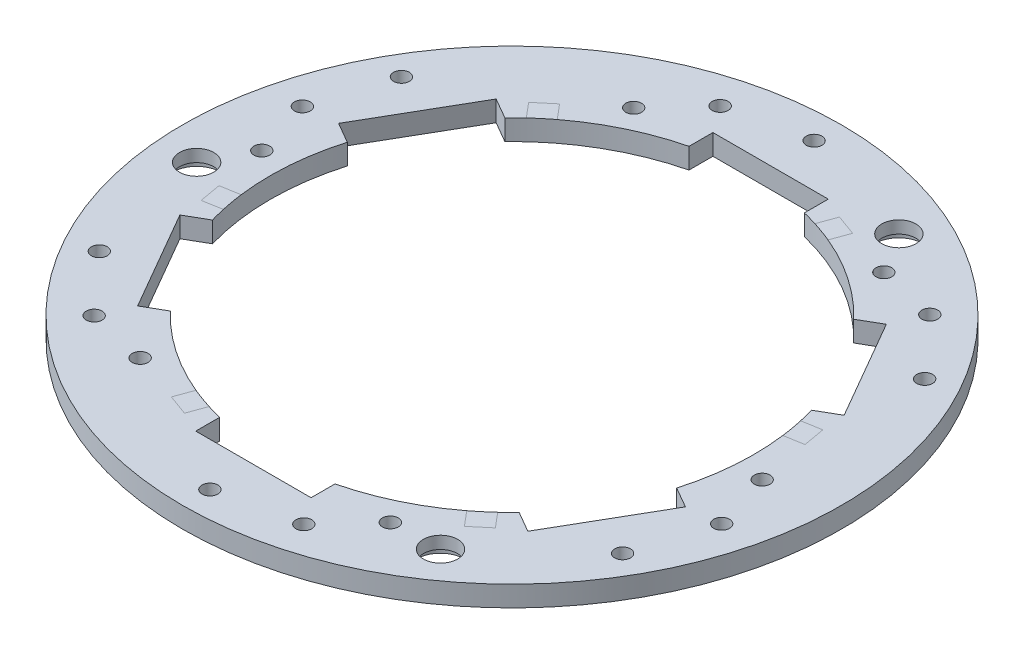
SolidWorks part; units mm, degrees
material "6061 Alloy"
ref_plane "Front Plane" through (0, 0, 0) normal (0, 0, 1) x (1, 0, 0)
ref_plane "Top Plane" through (0, 0, 0) normal (0, 1, 0) x (1, 0, 0)
ref_plane "Right Plane" through (0, 0, 0) normal (1, 0, 0) x (0, 0, -1)
sketch "Sketch1" plane through (0, 0, 0) normal (0, 1, 0) x (1, 0, 0)
  line L0 (-13.335, -54.2656) -> (-13.335, -58.1814)
  line L1 (13.335, -54.2656) -> (13.335, -58.1814)
  line L2 (-13.335, -59.7901) -> (13.335, -59.7901)
  line L3 (13.335, -58.1814) -> (13.335, -59.7901)
  line L4 (-13.335, -58.1814) -> (-13.335, -59.7901)
  line L5 (0, 0) -> (-67.0539, -5.8665) construction
  line L6 (0, 0) -> (0, -23.1086) construction
  line L7 (0, 0) -> (17.8146, -65.9496) construction
  line L8 (0, 0) -> (27.4515, -55.5868) construction
  circle A0 centre (0, 0) radius 55.88
  circle A1 centre (0, 0) radius 76.2
  circle A2 centre (0, 0) radius 59.69
  circle A3 centre (0, -69.85) radius 1.8288
  circle A4 centre (-67.0539, -5.8665) radius 3.9561
  circle A5 centre (17.8146, -65.9496) radius 1.8288
  circle A6 centre (27.4515, -55.5868) radius 1.8288
  dimension "D1" = 111.76
  dimension "D2" = 152.4
  dimension "D8" = 3.6576
  dimension "D11" = 7.9121
  dimension "D12" = 3.6576
  dimension "D15" = 3.6576
  dimension "D4" = 13.335
  dimension "D5" = 13.335
  dimension "D7" = 69.85
  dimension "D6" = 5.5245
  dimension "D9" = 67.31
  dimension "D10" = 85
  dimension "D13" = 17.8146
  dimension "D14" = 68.3133
  dimension "D16" = 61.9958
  dimension "D17" = 14.1512
  dimension "D3" = 3.81
extrude "Boss-Extrude1" add sketch "Sketch1" along normal blind 4.7625 contours L1 A2 L0 A0 | A1 A2 A0 region at (-15.0127, 0, 56.2235) region at (-74.0447, 0, 0)
pattern_circular "CirPattern1" count 6 over 360 about axis through (0, 4.7625, 0) along (0, 1, 0) of face at (-13.335, 2.3813, 57.0278) of face at (13.335, 2.3813, 57.0278) of face at (0, 4.7625, 71.6788) of face at (0, 2.3813, 59.7901)
sketch "Sketch2" plane through (0, 0, 0) normal (1, 0, 0) x (0, 0, -1)
  line L0 (76.2, 4.7625) -> (-76.2, 4.7625) construction
  line L1 (-76.2, 0) -> (76.2, 0) construction
  line L2 (76.2, 4.7625) -> (-76.2, 4.7625)
  line L3 (-76.2, 0) -> (76.2, 0)
  line L4 (0, 0) -> (0, 4.7625) construction
  circle A0 centre (-75.2856, 0) radius 2.667
  dimension "D1" = 5.334
  dimension "D2" = 0.9144
revolve "Cut-Revolve1" [suppressed] cut sketch "Sketch2" angle 360 about L4
sketch "Sketch4" plane through (0, 0, 0) normal (0, -1, 0) x (1, 0, 0)
  line L0 (0, 0) -> (-67.0539, 5.8665) construction
  line L1 (0, 0) -> (0, -39.7137) construction
  circle A0 centre (-67.0539, 5.8665) radius 5.588
  circle A2 centre (-67.0539, 5.8665) radius 3.9561 construction
  circle A3 centre (-67.0539, 5.8665) radius 3.9561
  dimension "D2" = 11.176
extrude "Cut-Extrude1" cut sketch "Sketch4" against normal blind 1.905 contours A0 region at (-72.4838, 0, 5.8665)
pattern_circular "CirPattern2" count 3 over 360 about axis through (0, 0, 0) along (0, 1, 0) of face at (-67.0539, 4.7625, 9.8225) of face at (-67.0539, 1.905, 1.9104) of face at (-67.0539, 1.905, 0.2785)
sketch "Sketch5" plane through (0, 4.7625, 0) normal (0, 1, 0) x (1, 0, 0)
  line L0 (0, 0) -> (-20.0894, -55.1952)
  line L1 (0, 0) -> (0, -18.6852)
  line L2 (-16.5968, -53.0258) -> (-18.2257, -57.5011)
  line L3 (-18.2257, -57.5011) -> (-22.9993, -55.7636)
  line L4 (-22.9993, -55.7636) -> (-21.3704, -51.2884)
  line L5 (-59.7924, -7.9638) -> (-55.1022, -7.1368)
  line L6 (-54.2201, -12.1397) -> (-58.9103, -12.9667)
  line L7 (-58.9103, -12.9667) -> (-59.7924, -7.9638)
  line L8 (-36.7931, 47.7998) -> (-33.7318, 44.1515)
  line L9 (-37.6233, 40.8862) -> (-40.6846, 44.5345)
  line L10 (-40.6846, 44.5345) -> (-36.7931, 47.7998)
  line L11 (22.9993, 55.7636) -> (21.3704, 51.2884)
  line L12 (16.5968, 53.0258) -> (18.2257, 57.5011)
  line L13 (18.2257, 57.5011) -> (22.9993, 55.7636)
  line L14 (59.7924, 7.9638) -> (55.1022, 7.1368)
  line L15 (54.2201, 12.1397) -> (58.9103, 12.9667)
  line L16 (58.9103, 12.9667) -> (59.7924, 7.9638)
  line L17 (36.7931, -47.7998) -> (33.7318, -44.1515)
  line L18 (37.6233, -40.8862) -> (40.6846, -44.5345)
  line L19 (40.6846, -44.5345) -> (36.7931, -47.7998)
  circle A0 centre (0, 0) radius 55.5625
  circle A1 centre (0, 0) radius 58.7375 construction
  circle A2 centre (0, 0) radius 55.5625
  circle A3 centre (0, 0) radius 55.5625
  circle A4 centre (0, 0) radius 55.5625
  circle A5 centre (0, 0) radius 55.5625
  circle A6 centre (0, 0) radius 55.5625
  point P38 (0, 0)
  dimension "D1" = 111.125
  dimension "D3" = 20
  dimension "D4" = 2.54
  dimension "D5" = 4.7625
  dimension "D6" = 2.54
  dimension "D2" = 3.175
  dimension "D7" = 6
split line "Split Line1"
pattern_circular "CirPattern3" count 6 over 360 about axis through (0, 4.7625, 0) along (0, 1, 0) of face at (17.8146, 4.7625, 67.7784)
pattern_circular "CirPattern5" count 6 over 360 about axis through (0, 4.7625, 0) along (0, 1, 0) of face at (27.4515, 4.7625, 57.4156)
equation "\"Middle Coupler Inner Daimeter\"= 3.875in"
equation "\"Middle Coupler  Wall Thickness\" = 0.25in"
equation "\"Middle Coupler Bottom Thickness\"= 0.2in"
equation "\"Bearing Rail Offset\"= 0.45in"
equation "\"3-56 UNF Tap\"= 0.089in"
equation "\"3-56 UNF Clearance\"= 0.104in"
equation "\"Ball Bearing Distance\"= 0.03in"
equation "\"D1@Sketch1\"=\"Middle Coupler Inner Daimeter\"+0.5+0.0125*2in"
equation "\"TCA Outer Diameter\" = 6in"
equation "\"D2@Sketch1\"=\"TCA Outer Diameter\""
equation "\"D4@Sketch1\"=0.50 + (0.05/2)"
equation "\"D5@Sketch1\"=\"D4@Sketch1\""
equation "\"D7@Sketch1\"=(\"D2@Sketch1\"-0.5)/2"
equation "\"D8@Sketch1\"=\"6-32 Clearance\""
equation "\"D2@Sketch2\"=\"Interstage Aeroframe Wall Thickness\"/2"
equation "\"Interstage Aeroframe Wall Thickness\" = 0.072in"
equation "\"Compression Spring OD\"= 0.42in"
equation "\"10-24 Tap\"= 0.157in"
equation "\"10-24 Clearance\"= 0.196in"
equation "\"D2@Sketch4\"=\"Compression Spring OD\"+0.02"
equation "\"D3@Sketch1\"=0.125in+(0.05/2)"
equation "\"Lower Stage Fuselage Wall Thickness\" = 0.25in"
equation "\"6-32 Tap\" = 0.107in"
equation "\"1/4-20 Tap\" = 0.201in"
equation "\"3-48 Tap\"= 0.079in"
equation "\"12-24 Tap\" = 0.177in"
equation "\"3-48 Clearance\" = 0.104in"
equation "\"6-32 Clearance\" = 0.144"
equation "\"D6@Sketch1\"=3/16 + 0.03"
equation "\"D9@Sketch1\"=(\"D2@Sketch1\"+\"D1@Sketch1\")/4+0.05"
equation "\"D11@Sketch1\"=5/16in - 0.001in"
equation "\"D1@Sketch5\"=\"Middle Coupler Inner Daimeter\"+0.5"
equation "\"D5@Sketch5\"=3/16"
equation "\"D6@Sketch5\"=\"D4@Sketch5\""
equation "\"D1@Boss-Extrude1\"=3/16"
